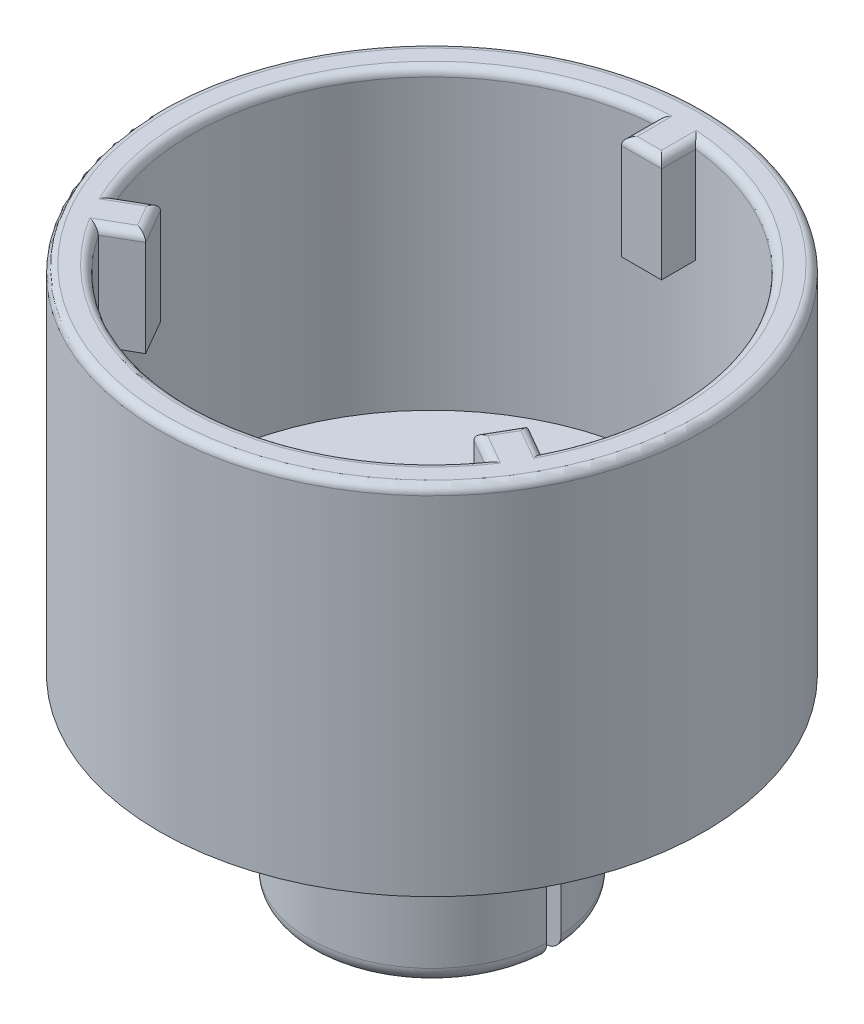
SolidWorks part; units mm, degrees
ref_plane "Front Plane" through (0, 0, 0) normal (0, 0, 1) x (1, 0, 0)
ref_plane "Top Plane" through (0, 0, 0) normal (0, 1, 0) x (1, 0, 0)
ref_plane "Right Plane" through (0, 0, 0) normal (1, 0, 0) x (0, 0, -1)
sketch "Sketch1" plane through (0, 0, 0) normal (0, 1, 0) x (1, 0, 0)
  circle A0 centre (0, 0) radius 34
  dimension "D1" = 68
extrude "Boss-Extrude1" add sketch "Sketch1" along normal blind 44.3
sketch "Sketch2" plane through (0, 44.3, 0) normal (0, 1, 0) x (1, 0, 0)
  circle A0 centre (0, 0) radius 30
  dimension "D1" = 60
extrude "Cut-Extrude1" cut sketch "Sketch2" against normal blind 37
sketch "Sketch3" plane through (0, 0, 0) normal (0, -1, 0) x (1, 0, 0)
  circle A0 centre (0, 0) radius 19.5
  dimension "D1" = 39
extrude "Boss-Extrude2" add sketch "Sketch3" along normal blind 7
sketch "Sketch4" plane through (0, -7, 0) normal (0, -1, 0) x (1, 0, 0)
  circle A0 centre (0, 0) radius 15.25
  dimension "D1" = 30.5
extrude "Boss-Extrude3" add sketch "Sketch4" along normal blind 16
fillet "Fillet1" radius 5 1 edges at (0, 0, -19.5)
sketch "Sketch5" plane through (0, 44.3, 0) normal (0, 1, 0) x (1, 0, 0)
  line L0 (-1.9905, 29.9339) -> (-1.9905, 25.6053)
  line L1 (-1.9905, 25.6053) -> (3.0302, 25.6053)
  line L2 (3.0302, 25.6053) -> (3.0302, 29.8466)
  line L3 (26.9188, -13.2431) -> (23.1701, -11.0788)
  line L4 (23.1701, -11.0788) -> (20.6597, -15.4269)
  line L5 (20.6597, -15.4269) -> (24.3328, -17.5475)
  line L6 (-24.9282, -16.6908) -> (-21.1796, -14.5265)
  line L7 (-21.1796, -14.5265) -> (-23.69, -10.1784)
  line L8 (-23.69, -10.1784) -> (-27.363, -12.299)
  circle A0 centre (0, 0) radius 30 construction
  arc A1 (24.3328, -17.5475) -> (26.9188, -13.2431) centre (0, 0) ccw
  circle A2 centre (0, 0) radius 30
  arc A3 (3.0302, 29.8466) -> (-1.9905, 29.9339) centre (0, 0) ccw
  arc A4 (-27.363, -12.299) -> (-24.9282, -16.6908) centre (0, 0) ccw
  point P19 (0, 0)
  dimension "D1" = 0
  dimension "D2" = 3
extrude "Boss-Extrude4" add sketch "Sketch5" against normal blind 13
sketch "Sketch7" plane through (0, -23, 0) normal (0, -1, 0) x (1, 0, 0)
  line L1 (33.0968, 0.9034) -> (-33.0968, 0.9034)
  line L2 (33.0968, 0.9034) -> (33.0968, -0.9034)
  line L3 (33.0968, -0.9034) -> (-33.0968, -0.9034)
  line L4 (-33.0968, 0.9034) -> (-33.0968, -0.9034)
  line L5 (33.0968, 0.9034) -> (-33.0968, -0.9034) construction
  line L6 (33.0968, -0.9034) -> (-33.0968, 0.9034) construction
  point P0 (0, 0)
extrude "Cut-Extrude2" cut sketch "Sketch7" against normal up to surface (16 mm away) up to face at (0, -7, -15.25)
fillet "Fillet2" radius 2 2 edges at (0, -23, 15.25) (0, -23, -15.25)
sketch "Sketch8" plane through (0, 7.3, 0) normal (0, 1, 0) x (1, 0, 0)
  circle A0 centre (0, 0) radius 10.3601
fillet "Fillet3" radius 1 4 edges at (26.2377, 44.3, -14.5459) (-25.716, 44.3, -15.4495) (-0.5217, 44.3, 29.9955) (0, 44.3, 34)
fillet "Fillet4" radius 1 9 edges at (-23.4879, 44.3, 15.8592) (-22.4348, 44.3, 12.3525) (-25.9617, 44.3, 11.49) (3.0302, 44.3, -28.2284) (-1.9905, 44.3, -28.2707) (0.5198, 44.3, -25.6053) (25.4784, 44.3, 12.4115) (21.9149, 44.3, 13.2529) (22.9314, 44.3, 16.7385)
